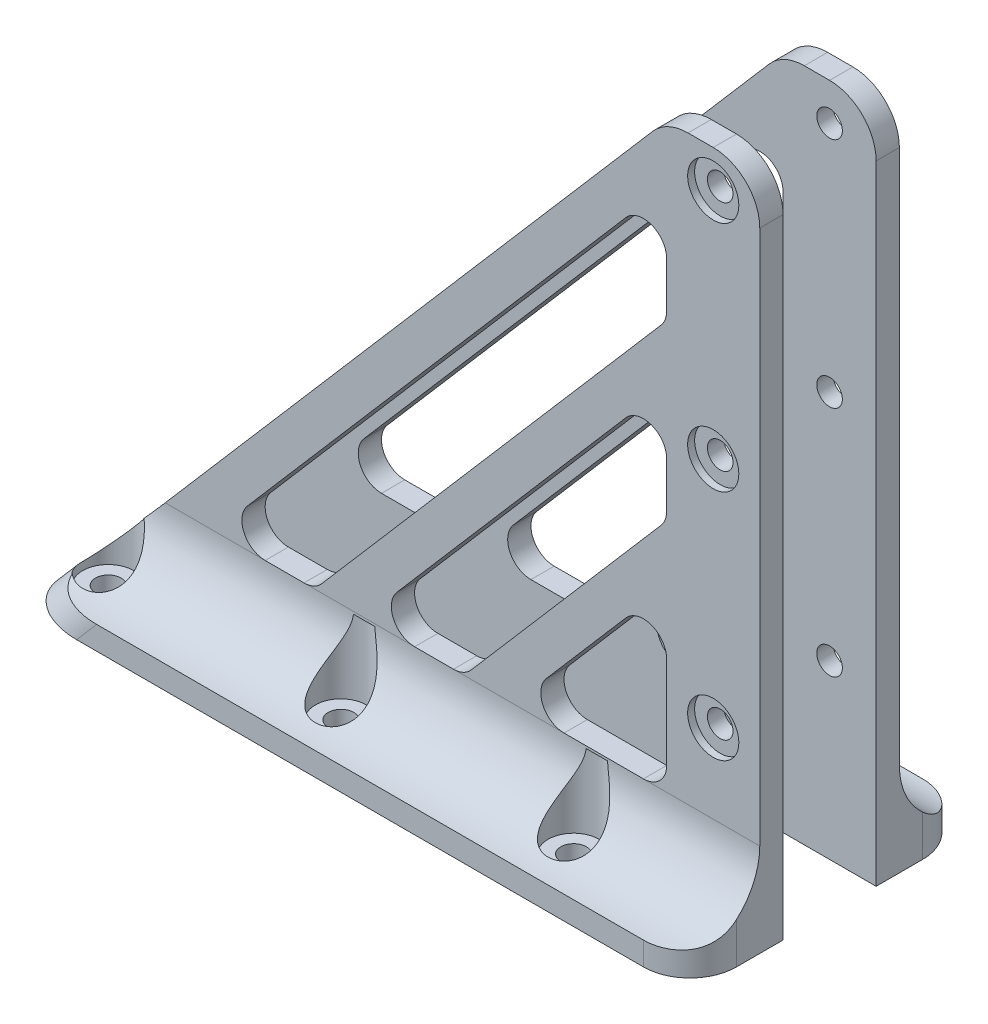
SolidWorks part; units mm, degrees
ref_plane "Front Plane" through (0, 0, 0) normal (0, 0, 1) x (1, 0, 0)
ref_plane "Top Plane" through (0, 0, 0) normal (0, 1, 0) x (1, 0, 0)
ref_plane "Right Plane" through (0, 0, 0) normal (1, 0, 0) x (0, 0, -1)
sketch "Sketch1" plane through (0, 0, 0) normal (0, 0, 1) x (1, 0, 0)
  line L0 (0, 0) -> (-145, 0)
  line L2 (0, 145) -> (0, 0)
  line L3 (0, 145) -> (-20, 145)
  line L4 (-20, 145) -> (-145, 0)
  dimension "D1" = 145
  dimension "D2" = 20
extrude "Boss-Extrude1" add sketch "Sketch1" along normal blind 5
sketch "Sketch4" plane through (0, 0, 0) normal (0, -1, 0) x (1, 0, 0)
  line L1 (-145, 5) -> (0, 5)
  line L2 (-145, 5) -> (-145, 20)
  line L3 (-145, 20) -> (0, 20)
  line L4 (0, 5) -> (0, 20)
  line L5 (-145, 0) -> (0, 0) construction
  point P5 (0, 4)
  dimension "D1" = 20
extrude "Boss-Extrude2" add sketch "Sketch4" against normal blind 5
sketch "Sketch5" plane through (0, 0, 5) normal (0, 0, -1) x (-1, 0, 0)
  line L0 (145, 5) -> (145, 0)
  line L1 (145, 0) -> (140.6897, 5)
  line L2 (140.6897, 5) -> (145, 5)
extrude "Cut-Extrude1" cut sketch "Sketch5" against normal blind 25
sketch "Sketch6" plane through (0, 0, 5) normal (0, 0, 1) x (1, 0, 0)
  line L0 (0, 5) -> (0, 145) construction
  line L1 (0, 145) -> (-20, 145) construction
  circle A0 centre (-10, 137) radius 2.75
  circle A1 centre (-10, 87) radius 2.75
  circle A2 centre (-10, 37) radius 2.75
  dimension "D1" = 5.5
  dimension "D2" = 10
  dimension "D3" = 8
  dimension "D4" = 3
extrude "Cut-Extrude2" cut sketch "Sketch6" against normal blind 25
sketch "Sketch7" plane through (0, 0, 0) normal (0, -1, 0) x (1, 0, 0)
  line L0 (-145, 20) -> (-145, 0) construction
  circle A0 centre (-135, 10) radius 2.75
  circle A1 centre (-85, 10) radius 2.75
  circle A2 centre (-35, 10) radius 2.75
  point P4 (-145, 10)
  dimension "D1" = 5.5
  dimension "D2" = 10
  dimension "D3" = 3
extrude "Cut-Extrude3" cut sketch "Sketch7" against normal blind 25
fillet "Fillet1" radius 15 1 edges at (-70.3448, 5, 5)
fillet "Fillet2" radius 10 4 edges at (0, 145, 2.5) (-20, 145, 2.5) (0, 2.5, 20) (-142.8448, 2.5, 20)
sketch "Sketch8" plane through (0, 0, 0) normal (0, -1, 0) x (1, 0, 0)
  circle A0 centre (-135, 10) radius 5.5
  circle A1 centre (-85, 10) radius 5.5
  circle A2 centre (-35, 10) radius 5.5
  dimension "D1" = 11
extrude "Cut-Extrude4" cut sketch "Sketch8" against normal blind 16 from offset 3.5 offset against normal yes
sketch "Sketch9" plane through (0, 0, 5) normal (0, 0, 1) x (1, 0, 0)
  circle A0 centre (-10, 37) radius 5.5
  circle A1 centre (-10, 87) radius 5.5
  circle A2 centre (-10, 137) radius 5.5
  dimension "D1" = 11
extrude "Cut-Extrude5" cut sketch "Sketch9" against normal offset from surface (1.5 mm away) 3.5 up to face at (-12.75, 137, 0)
sketch "Sketch10" plane through (0, 0, 5) normal (0, 0, 1) x (1, 0, 0)
  line L0 (-117.1963, 20) -> (-20, 132.7477)
  line L2 (-20, 132.7477) -> (-20, 107.7477)
  line L3 (-20, 20) -> (-52.9682, 20)
  line L4 (-127.7586, 20) -> (0, 20) construction
  line L5 (-22.9919, 141.5294) -> (-127.7586, 20) construction
  line L6 (0, 20) -> (0, 135) construction
  line L7 (-95.6446, 20) -> (-20, 107.7477)
  line L8 (-85.0823, 20) -> (-20, 95.4954)
  line L9 (-52.9682, 20) -> (-20, 58.2432)
  line L10 (-63.5305, 20) -> (-20, 70.4954)
  line L11 (-20, 95.4954) -> (-20, 70.4954)
  line L12 (-20, 58.2432) -> (-20, 20)
  line L13 (-63.5305, 20) -> (-85.0823, 20)
  line L14 (-95.6446, 20) -> (-117.1963, 20)
  point P17 (0, 0)
  point P18 (-20, 61.8984)
  point P19 (-20, 68.8857)
  dimension "D1" = 8
  dimension "D2" = 20
  dimension "D3" = 8
  dimension "D4" = 8
  dimension "D5" = 25
  dimension "D6" = 25
extrude "Cut-Extrude6" cut sketch "Sketch10" against normal blind 8
fillet "Fillet3" radius 5 11 edges at (-52.9682, 20, 2.5) (-85.0823, 20, 2.5) (-117.1963, 20, 2.5) (-20, 58.2432, 2.5) (-20, 95.4954, 2.5) (-20, 132.7477, 2.5) (-95.6446, 20, 2.5) (-63.5305, 20, 2.5) (-20, 20, 2.5) (-20, 70.4954, 2.5) (-20, 107.7477, 2.5)
ref_plane "Plane2" through (0, 0, -10) normal (0, 0, -1) x (-1, 0, 0)
mirror "Mirror2" about plane through (0, 0, -10) normal (0, 0, -1) of bodies 108
